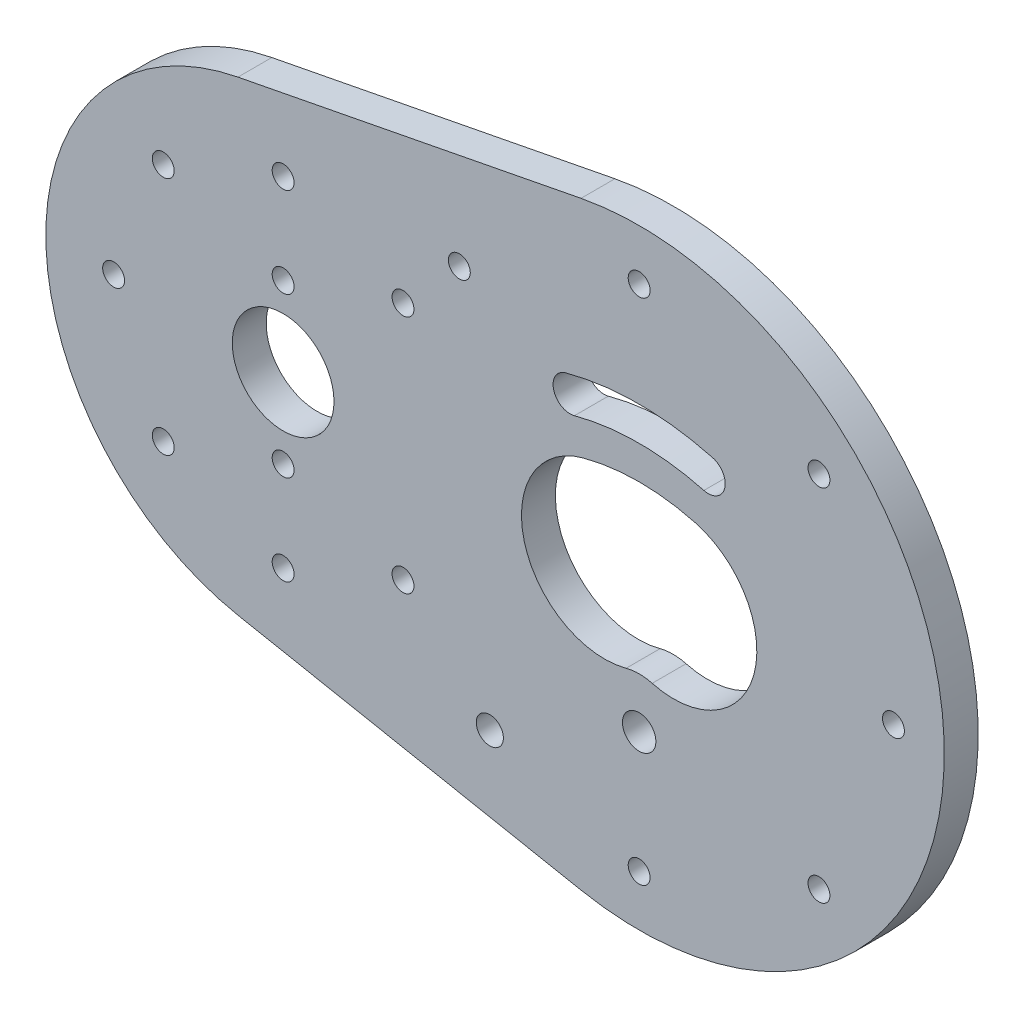
SolidWorks part; units mm, degrees
ref_plane "Front Plane" through (0, 0, 0) normal (0, 0, 1) x (1, 0, 0)
ref_plane "Top Plane" through (0, 0, 0) normal (0, 1, 0) x (1, 0, 0)
ref_plane "Right Plane" through (0, 0, 0) normal (1, 0, 0) x (0, 0, -1)
sketch "Sketch1" plane through (0, 0, 0) normal (0, 0, 1) x (1, 0, 0)
  line L0 (0, 0) -> (0, 36.4546) construction
  line L1 (0, 0) -> (-10.2847, 38.3829) construction
  line L2 (-33.3375, 12.5) -> (0, 12.5) construction
  line L4 (-91.5313, 56.95) -> (35.4687, 56.95)
  line L5 (-91.5313, 56.95) -> (-91.5313, -31.95)
  line L6 (-91.5313, -31.95) -> (35.4687, -31.95)
  line L7 (35.4687, 56.95) -> (35.4687, -31.95)
  line L8 (-91.5313, 56.95) -> (35.4687, -31.95) construction
  line L9 (-91.5313, -31.95) -> (35.4687, 56.95) construction
  arc A0 (5.2502, 19.5939) -> (1.2203, 4.5542) centre (3.2352, 12.0741) cw
  arc A1 (5.2502, 19.5939) -> (-5.2502, 19.5939) centre (0, 0) ccw
  circle A2 centre (0, 12.5) radius 12.5 construction
  circle A3 centre (0, 0) radius 1.5649
  arc A4 (10.8253, 6.25) -> (-10.8253, 6.25) centre (0, 0) ccw construction
  arc A5 (1.2203, 4.5542) -> (-1.2203, 4.5542) centre (0, 0) ccw
  arc A6 (-5.2502, 19.5939) -> (-1.2203, 4.5542) centre (-3.2352, 12.0741) ccw
  circle A7 centre (0, 25) radius 1.5875 construction
  arc A8 (6.8814, 25.6816) -> (-6.8814, 25.6816) centre (0, 0) ccw
  arc A9 (6.0596, 22.6147) -> (-6.0596, 22.6147) centre (0, 0) ccw
  circle A10 centre (0, 0) radius 25 construction
  arc A11 (-6.8814, 25.6816) -> (-6.0596, 22.6147) centre (-6.4705, 24.1481) ccw
  arc A12 (6.8814, 25.6816) -> (6.0596, 22.6147) centre (6.4705, 24.1481) cw
  circle A13 centre (-33.3375, 12.5) radius 4.7625
  circle A14 centre (-33.3375, 12.5) radius 25.4 construction
  point P0 (0, 0)
  point P18 (-28.0313, 12.5)
  dimension "D4" = 25
  dimension "D6" = 50.8
  dimension "D2" = 3.175
  dimension "D3" = 9.525
  dimension "D9" = 7.7851
  dimension "D1" = 15
  dimension "D5" = 33.3375
  dimension "D7" = 88.9
  dimension "D8" = 127
extrude "Boss-Extrude1" add sketch "Sketch1" along normal blind 3.175
sketch "Sketch2" plane through (0, 0, 3.175) normal (0, 0, 1) x (1, 0, 0)
  line L0 (-33.3375, 12.5) -> (43.934, 12.5) construction
  line L1 (0, 0) -> (0, 70.9306) construction
  line L2 (-37.5708, 34.3181) -> (-5.4429, 40.5518)
  line L3 (-37.5708, -9.3181) -> (-5.4429, -15.5518)
  line L5 (-107.0175, 80.3674) -> (70.5021, 80.3674)
  line L6 (-107.0175, 80.3674) -> (-107.0175, -46.3508)
  line L7 (-107.0175, -46.3508) -> (70.5021, -46.3508)
  line L8 (70.5021, 80.3674) -> (70.5021, -46.3508)
  arc A0 (-5.4429, -15.5518) -> (-5.4429, 40.5518) centre (0, 12.5) ccw
  arc A1 (-37.5708, 34.3181) -> (-37.5708, -9.3181) centre (-33.3375, 12.5) ccw
  dimension "D1" = 57.15
  dimension "D2" = 44.45
extrude "Cut-Extrude1" cut sketch "Sketch2" against normal through all
sketch "Sketch4" plane through (0, 0, 3.175) normal (0, 0, 1) x (1, 0, 0)
  line L0 (-33.3375, 12.5) -> (35.849, 12.5) construction
  line L1 (0, 0) -> (0, 48.1146) construction
  circle A0 centre (-33.3375, 12.5) radius 15.875 construction
  circle A1 centre (0, 12.5) radius 23.8125 construction
  circle A2 centre (-33.3375, 28.375) radius 0.635
  circle A3 centre (0, 36.3125) radius 0.635
  circle A4 centre (-22.1122, 23.7253) radius 0.635
  circle A5 centre (-17.4625, 12.5) radius 0.635 [skipped]
  circle A6 centre (-13.9821, -6.8554) radius 1.27
  circle A7 centre (-22.1122, 1.2747) radius 0.635
  circle A8 centre (-33.3375, -3.375) radius 0.635
  circle A9 centre (-44.5628, 1.2747) radius 0.635
  circle A10 centre (-49.2125, 12.5) radius 0.635
  circle A11 centre (16.838, 29.338) radius 0.635
  circle A12 centre (23.8125, 12.5) radius 0.635
  circle A13 centre (16.838, -4.338) radius 0.635
  circle A14 centre (0, -11.3125) radius 0.635
  circle A15 centre (-44.5628, 23.7253) radius 0.635
  circle A16 centre (-23.8125, 12.5) radius 0.635 [skipped]
  circle A17 centre (-16.838, 29.338) radius 0.635
  circle A18 centre (-16.838, -4.338) radius 0.635 [skipped]
  dimension "D1" = 47.625
  dimension "D2" = 31.75
  dimension "D3" = 1.27
  dimension "D4" = 1.27
  dimension "D6" = 8
  dimension "D5" = 8
extrude "Cut-Extrude2" cut sketch "Sketch4" against normal through all
sketch "Sketch5" plane through (0, 0, 3.175) normal (0, 0, 1) x (1, 0, 0)
  circle A0 centre (-33.3375, 12.5) radius 7.4422 construction
  circle A1 centre (-33.3375, 19.9422) radius 0.635
  circle A2 centre (-33.3375, 5.0578) radius 0.635
  dimension "D1" = 14.8844
  dimension "D2" = 1.27
  dimension "D3" = 1.27
extrude "Cut-Extrude3" cut sketch "Sketch5" against normal through all
hole_wizard "M2.5x0.45 Tapped Hole2" positions "3DSketch2" profile "Sketch6" tap size "M2.5x0.45" standard "Ansi Metric"
sketch3d "3DSketch2"
  line L0 (-44.5628, 23.7253, 0) -> (-44.5628, 23.7253, 3.175) construction
  line L1 (-49.2125, 12.5, 0) -> (-49.2125, 12.5, 3.175) construction
  line L2 (-44.5628, 1.2747, 0) -> (-44.5628, 1.2747, 3.175) construction
  line L3 (-33.3375, -3.375, 0) -> (-33.3375, -3.375, 3.175) construction
  line L4 (-22.1122, 1.2747, 0) -> (-22.1122, 1.2747, 3.175) construction
  line L5 (-22.1122, 23.7253, 0) -> (-22.1122, 23.7253, 3.175) construction
  line L6 (-33.3375, 28.375, 0) -> (-33.3375, 28.375, 3.175) construction
  line L7 (-16.838, 29.338, 0) -> (-16.838, 29.338, 3.175) construction
  line L8 (16.838, 29.338, 0) -> (16.838, 29.338, 3.175) construction
  line L9 (23.8125, 12.5, 0) -> (23.8125, 12.5, 3.175) construction
  line L10 (16.838, -4.338, 0) -> (16.838, -4.338, 3.175) construction
  line L11 (0, -11.3125, 0) -> (0, -11.3125, 3.175) construction
  line L12 (0, 36.3125, 0) -> (0, 36.3125, 3.175) construction
  line L13 (-33.3375, 19.9422, 0) -> (-33.3375, 19.9422, 3.175) construction
  line L14 (-33.3375, 5.0578, 0) -> (-33.3375, 5.0578, 3.175) construction
  point P0 (-44.5628, 23.7253, 3.175)
  point P4 (-49.2125, 12.5, 3.175)
  point P8 (-44.5628, 1.2747, 3.175)
  point P12 (-33.3375, -3.375, 3.175)
  point P16 (-22.1122, 1.2747, 3.175)
  point P20 (-22.1122, 23.7253, 3.175)
  point P24 (-33.3375, 28.375, 3.175)
  point P28 (-16.838, 29.338, 3.175)
  point P37 (16.838, 29.338, 3.175)
  point P41 (23.8125, 12.5, 3.175)
  point P45 (16.838, -4.338, 3.175)
  point P49 (0, -11.3125, 3.175)
  point P55 (0, 36.3125, 3.175)
  point P60 (-33.3375, 19.9422, 3.175)
  point P64 (-33.3375, 5.0578, 3.175)
sketch "Sketch6" plane through (-44.5628, 23.7253, 3.175) normal (1, 0, 0) x (0, -1, 0)
  line L0 (0, 0) -> (0, 7.9819)
  line L1 (0, 7.9819) -> (1.025, 7.366)
  line L2 (1.025, 7.366) -> (1.025, 0)
  line L5 (1.025, 0) -> (0, 0)
  line L10 (0, 7.9819) -> (-1.025, 7.366) construction
  line L11 (0, -6.35) -> (0, 107.95) construction
  dimension "Tap Drill Dia." = 2.05
  dimension "Tap Drill Depth" = 7.366
  dimension "Drill Angle" = 118
cosmetic thread "Hole Thread1" parameters "D1"=2.54, "D2"=2.5
cosmetic thread "Hole Thread2" parameters "D1"=2.54, "D2"=2.5
cosmetic thread "Hole Thread3" parameters "D1"=2.54, "D2"=2.5
cosmetic thread "Hole Thread4" parameters "D1"=2.54, "D2"=2.5
cosmetic thread "Hole Thread6" parameters "D1"=2.54, "D2"=2.5
cosmetic thread "Hole Thread7" parameters "D1"=2.54, "D2"=2.5
cosmetic thread "Hole Thread8" parameters "D1"=2.54, "D2"=2.5
cosmetic thread "Hole Thread9" parameters "D1"=2.54, "D2"=2.5
cosmetic thread "Hole Thread10" parameters "D1"=2.54, "D2"=2.5
cosmetic thread "Hole Thread11" parameters "D1"=2.54, "D2"=2.5
cosmetic thread "Hole Thread12" parameters "D1"=2.54, "D2"=2.5
cosmetic thread "Hole Thread13" parameters "D1"=2.54, "D2"=2.5
cosmetic thread "Hole Thread14" parameters "D1"=2.54, "D2"=2.5
cosmetic thread "Hole Thread15" parameters "D1"=2.54, "D2"=2.5
cosmetic thread "Hole Thread16" parameters "D1"=2.54, "D2"=2.5
